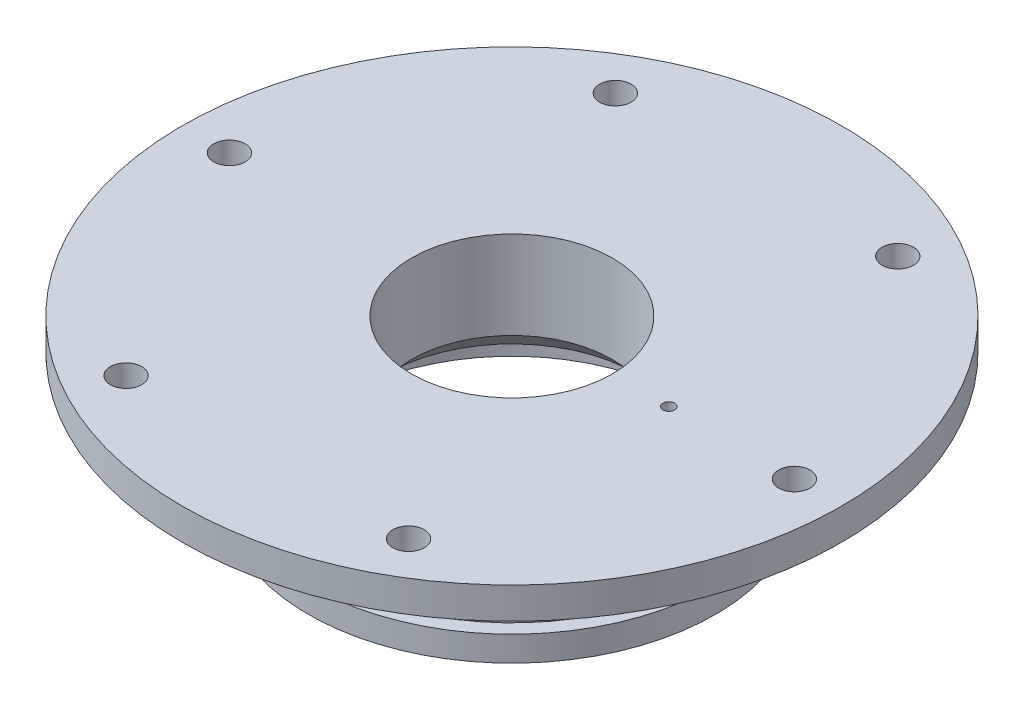
SolidWorks part; units mm, degrees
material "6061-T6 (SS)"
ref_plane "Front Plane" through (0, 0, 0) normal (0, 0, 1) x (1, 0, 0)
ref_plane "Top Plane" through (0, 0, 0) normal (0, 1, 0) x (1, 0, 0)
ref_plane "Right Plane" through (0, 0, 0) normal (1, 0, 0) x (0, 0, -1)
ref_axis "Axis1" through (0, -0.4763, 0) along (0, 1, 0)
ref_plane "Plane2" through (0, 0, 0) normal (0.5, 0, 0.866) x (0, 1, 0)
sketch "Sketch1" plane through (0, 0, 0) normal (0, 1, 0) x (1, 0, 0)
  circle A0 centre (0, 0) radius 66.675
  circle A1 centre (0, 0) radius 20.32
  dimension "D1" = 133.35
  dimension "D2" = 40.64
extrude "Boss-Extrude1" add sketch "Sketch1" along normal blind 6.35
sketch "Sketch2" plane through (0, 0, 0) normal (0, 0, 1) x (1, 0, 0)
  line L1 (41.275, 0) -> (44.45, 0)
  line L2 (41.275, 0) -> (41.275, 3.81)
  line L3 (41.275, 3.81) -> (44.45, 3.81)
  line L4 (44.45, 0) -> (44.45, 3.81)
  line L6 (73.3425, 0) -> (-73.3425, 0) construction
  dimension "D1" = 3.81
  dimension "D2" = 3.175
  dimension "D3" = 44.45
revolve "Cut-Revolve1" [suppressed] cut sketch "Sketch2" angle 360 about axis through (0, -0.4763, 0) along (0, 1, 0)
hole_wizard "1/4 (0.25) Diameter Hole1" positions "Sketch5" profile "Sketch4" hole size "1/4" standard "ANSI Inch" end condition up to next
sketch "Sketch5" plane through (0, 6.35, 0) normal (0, 1, 0) x (1, 0, 0)
  line L0 (-17.4625, 0) -> (17.4625, 0) construction
  point P0 (57.15, 0)
  dimension "D1" = 57.15
sketch "Sketch4" plane through (57.15, 6.35, 0) normal (1, 0, 0) x (0, 0, 1)
  line L0 (0, 0) -> (0, 6.351)
  line L1 (0, 6.351) -> (3.175, 6.351)
  line L2 (3.175, 6.351) -> (3.175, 0)
  line L5 (3.175, 0) -> (0, 0)
  line L11 (0, -6.35) -> (0, 107.95) construction
  dimension "Thru Hole Dia." = 6.35
  dimension "Thru Hole Depth" = 6.351
pattern_circular "CirPattern1" count 6 over 360 about axis through (0, -0.4763, 0) along (0, 1, 0) of "1/4 (0.25) Diameter Hole1"
sketch "Sketch6" plane through (0, 0, 0) normal (0, -1, 0) x (1, 0, 0)
  circle A0 centre (0, 0) radius 20.32
  circle A1 centre (0, 0) radius 41.148
  dimension "D1" = 82.296
  dimension "D2" = 40.64
extrude "Boss-Extrude2" add sketch "Sketch6" along normal blind 25.4
ref_plane "Plane1" through (0, -25.4, 0) normal (-1, 0, 0) x (0, 0, 1)
sketch "Sketch9" plane through (0, 0, 0) normal (0, 0, 1) x (1, 0, 0)
  line L0 (0, -0.4763) -> (0, 10.0012) construction
  line L1 (41.275, -20.32) -> (38.3413, -20.32)
  line L2 (41.275, -20.32) -> (41.275, -15.24)
  line L3 (41.275, -15.24) -> (38.3413, -15.24)
  line L4 (38.3413, -20.32) -> (38.3413, -15.24)
  line L8 (-41.148, -25.4) -> (41.148, -25.4) construction
  dimension "D1" = 38.3413
  dimension "D2" = 5.08
  dimension "D3" = 41.275
  dimension "D4" = 5.08
revolve "Cut-Revolve3" cut sketch "Sketch9" angle 360 about axis through (0, -0.4763, 0) along (0, 1, 0)
pattern_linear "LPattern1" [suppressed] count 2 spacing 10.16 of bodies 107
hole_wizard "1/4-20 Tapped Hole1" positions "3DSketch1" profile "Sketch10" tap size "1/4-20" standard "ANSI Inch"
sketch3d "3DSketch1"
  point P0 (-35.6352, -7.62, 20.574)
  point P1 (0, 0, 0)
  point P2 (0, 0, 0)
  dimension "D1" = 7.62
cosmetic thread "Hole Thread1" parameters "D1"=8.89, "D2"=6.35
sketch "Sketch10" plane through (-35.6352, -7.62, 20.574) normal (0, 1, 0) x (0.5, 0, 0.866)
  line L0 (0, 0) -> (0, 14.2338)
  line L1 (0, 14.2338) -> (2.5527, 12.7)
  line L2 (2.5527, 12.7) -> (2.5527, 0)
  line L5 (2.5527, 0) -> (0, 0)
  line L10 (0, 14.2338) -> (-2.5527, 12.7) construction
  line L11 (0, -6.35) -> (0, 107.95) construction
  dimension "Tap Drill Dia." = 5.1054
  dimension "Tap Drill Depth" = 12.7
  dimension "Drill Angle" = 118
pattern_circular "CirPattern2" count 6 over 360 about axis through (0, -0.4763, 0) along (0, 1, 0) of "1/4-20 Tapped Hole1"
hole_wizard "3/32 (0.09375) Diameter Hole1" positions "Sketch11" profile "Sketch12" hole size "3/32" standard "ANSI Inch" end condition through all
sketch "Sketch11" plane through (0, 6.35, 0) normal (0, 1, 0) x (1, 0, 0)
  line L1 (-17.4625, 0) -> (17.4625, 0) construction
  point P0 (31.75, 0)
  point P7 (0, 0)
  dimension "D1" = 31.75
sketch "Sketch12" plane through (31.75, 6.35, 0) normal (1, 0, 0) x (0, 0, 1)
  line L0 (0, 0) -> (0, 31.75)
  line L1 (0, 31.75) -> (1.1906, 31.75)
  line L2 (1.1906, 31.75) -> (1.1906, 0)
  line L5 (1.1906, 0) -> (0, 0)
  line L11 (0, -6.35) -> (0, 107.95) construction
  dimension "Thru Hole Dia." = 2.3812
  dimension "Thru Hole Depth" = 31.75
sketch "Sketch13" plane through (0, -25.4, 0) normal (0, -1, 0) x (1, 0, 0)
  circle A0 centre (0, 0) radius 34.925
  dimension "D1" = 69.85
extrude "Cut-Extrude1" cut sketch "Sketch13" against normal blind 8.89
chamfer "Chamfer1" [suppressed] distance 6.35 angle 60
chamfer "Chamfer2" distance 5.08 angle 45 1 edges at (0, -16.51, -20.32)
